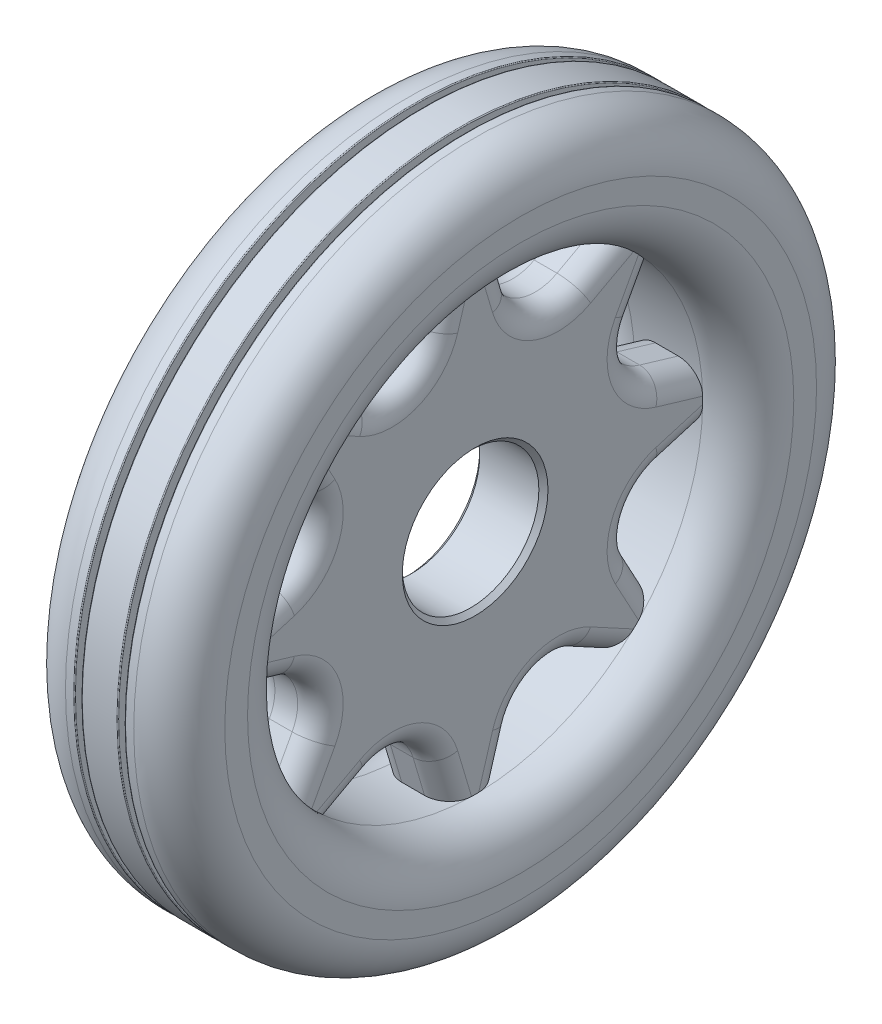
SolidWorks part; units mm, degrees
ref_plane "Front Plane" through (0, 0, 0) normal (0, 0, 1) x (1, 0, 0)
ref_plane "Top Plane" through (0, 0, 0) normal (0, 1, 0) x (1, 0, 0)
ref_plane "Right Plane" through (0, 0, 0) normal (1, 0, 0) x (0, 0, -1)
sketch "Sketch2" plane through (0, 0, 0) normal (0, 0, 1) x (1, 0, 0)
  line L0 (-23.7871, 0) -> (24.6428, 0) construction
  line L1 (24.6428, 0) -> (22.5464, 2.0963) construction
  line L2 (0, 0) -> (0, 50) construction
  line L3 (-7.5, 50) -> (7.5, 50)
  line L4 (17.5, 60) -> (17.5, 65)
  line L5 (7.5, 75) -> (-7.5, 75)
  line L6 (-17.5, 60) -> (-17.5, 65)
  arc A0 (17.5, 65) -> (7.5, 75) centre (7.5, 65) ccw
  arc A1 (7.5, 50) -> (17.5, 60) centre (7.5, 60) ccw
  arc A2 (-17.5, 65) -> (-7.5, 75) centre (-7.5, 65) cw
  arc A3 (-7.5, 50) -> (-17.5, 60) centre (-7.5, 60) cw
  point P11 (17.5, 75)
  point P14 (17.5, 50)
  point P16 (0, 75)
  dimension "D3" = 10
  dimension "D1" = 150
  dimension "D2" = 25
  dimension "D4" = 35
revolve "Revolve1" add sketch "Sketch2" angle 360 about L0
sketch "Sketch3" plane through (0, 0, 0) normal (1, 0, 0) x (0, 0, -1)
  line L0 (6, 50) -> (-6, 50)
  line L1 (-6, 50) -> (-12.1468, 29.3249)
  line L2 (0, 0) -> (0, 23.674) construction
  line L3 (6, 50) -> (12.1468, 29.3249)
  line L4 (31.1127, 39.598) -> (12.1468, 29.3249)
  line L5 (39.598, 31.1127) -> (29.3249, 12.1468)
  line L6 (39.598, 31.1127) -> (31.1127, 39.598)
  line L7 (50, 6) -> (29.3249, 12.1468)
  line L8 (50, -6) -> (29.3249, -12.1468)
  line L9 (50, -6) -> (50, 6)
  line L10 (39.598, -31.1127) -> (29.3249, -12.1468)
  line L11 (31.1127, -39.598) -> (12.1468, -29.3249)
  line L12 (31.1127, -39.598) -> (39.598, -31.1127)
  line L13 (6, -50) -> (12.1468, -29.3249)
  line L14 (-6, -50) -> (-12.1468, -29.3249)
  line L15 (-6, -50) -> (6, -50)
  line L16 (-31.1127, -39.598) -> (-12.1468, -29.3249)
  line L17 (-39.598, -31.1127) -> (-29.3249, -12.1468)
  line L18 (-39.598, -31.1127) -> (-31.1127, -39.598)
  line L19 (-50, -6) -> (-29.3249, -12.1468)
  line L20 (-50, 6) -> (-29.3249, 12.1468)
  line L21 (-50, 6) -> (-50, -6)
  line L22 (-39.598, 31.1127) -> (-29.3249, 12.1468)
  line L23 (-31.1127, 39.598) -> (-12.1468, 29.3249)
  line L24 (-31.1127, 39.598) -> (-39.598, 31.1127)
  line L25 (0, 22.7455) -> (9.5256, 17.5859)
  line L26 (-16.0835, 16.0835) -> (-19.1707, 5.6995)
  line L27 (-16.0835, 16.0835) -> (-5.6995, 19.1707)
  line L28 (-22.7455, 0) -> (-17.5859, -9.5256)
  line L29 (-22.7455, 0) -> (-17.5859, 9.5256)
  line L30 (-16.0835, -16.0835) -> (-5.6995, -19.1707)
  line L31 (-16.0835, -16.0835) -> (-19.1707, -5.6995)
  line L32 (0, -22.7455) -> (9.5256, -17.5859)
  line L33 (0, -22.7455) -> (-9.5256, -17.5859)
  line L34 (16.0835, -16.0835) -> (19.1707, -5.6995)
  line L35 (16.0835, -16.0835) -> (5.6995, -19.1707)
  line L36 (22.7455, 0) -> (17.5859, 9.5256)
  line L37 (22.7455, 0) -> (17.5859, -9.5256)
  line L38 (16.0835, 16.0835) -> (5.6995, 19.1707)
  line L39 (16.0835, 16.0835) -> (19.1707, 5.6995)
  line L40 (0, 22.7455) -> (-9.5256, 17.5859)
  circle A0 centre (0, 0) radius 50 construction
  circle A1 centre (0, 0) radius 20
  point P10 (0, 50)
  point P41 (0, 0)
  dimension "D2" = 40
  dimension "D1" = 6
  dimension "D3" = 8
extrude "Boss-Extrude1" add sketch "Sketch3" along normal blind 7.5 and the other way blind 7.5 contours L3 L4 L6 L5 L7 L9 L8 L10 L12 L11 L13 L15 L14 L16 L18 L17 L19 L21 L20 L22 L24 L23 L1 L0
fillet "Fillet1" radius 10 8 edges at (0, 29.3249, 12.1468) (0, 12.1468, 29.3249) (0, -12.1468, 29.3249) (0, -29.3249, 12.1468) (0, -29.3249, -12.1468) (0, -12.1468, -29.3249) (0, 12.1468, -29.3249) (0, 29.3249, -12.1468)
sketch "Sketch4" plane through (7.5, 0, 0) normal (1, 0, 0) x (0, 0, -1)
  circle A0 centre (0, 0) radius 15
  dimension "D1" = 30
extrude "Cut-Extrude1" cut sketch "Sketch4" against normal blind 20 and the other way blind 7.5
chamfer "Chamfer1" distance 1 angle 45 2 edges at (-7.5, 0, -15) (7.5, 0, -15)
fillet "Fillet2" radius 5 48 edges at (7.5, -37.3031, 26.8759) (7.5, -45.3814, 7.3731) (7.5, 7.3731, -45.3814) (7.5, 26.8759, -37.3031) (7.5, -26.8759, -37.3031) (7.5, -7.3731, -45.3814) (7.5, -45.3814, -7.3731) (7.5, -37.3031, -26.8759) (7.5, -7.3731, 45.3814) (7.5, -26.8759, 37.3031) (7.5, 26.8759, 37.3031) (7.5, 7.3731, 45.3814) (7.5, 45.3814, 7.3731) (7.5, 37.3031, 26.8759) (-7.5, 37.3031, 26.8759) (-7.5, 45.3814, 7.3731) (-7.5, 7.3731, 45.3814) (-7.5, 26.8759, 37.3031) (-7.5, -26.8759, 37.3031) (-7.5, -7.3731, 45.3814) (-7.5, -45.3814, 7.3731) (-7.5, -37.3031, 26.8759) (-7.5, -37.3031, -26.8759) (-7.5, -45.3814, -7.3731) (-7.5, -7.3731, -45.3814) (-7.5, -26.8759, -37.3031) (-7.5, 26.8759, -37.3031) (-7.5, 7.3731, -45.3814) (-7.5, 45.3814, -7.3731) (-7.5, 37.3031, -26.8759) (7.5, 37.3031, -26.8759) (7.5, 45.3814, -7.3731) (7.5, -34.7486, 14.3933) (7.5, 14.3933, -34.7486) (7.5, -14.3933, -34.7486) (7.5, -34.7486, -14.3933) (7.5, -14.3933, 34.7486) (7.5, 14.3933, 34.7486) (7.5, 34.7486, 14.3933) (-7.5, 34.7486, 14.3933) (-7.5, 14.3933, 34.7486) (-7.5, -14.3933, 34.7486) (-7.5, -34.7486, 14.3933) (-7.5, -34.7486, -14.3933) (-7.5, -14.3933, -34.7486) (-7.5, 14.3933, -34.7486) (-7.5, 34.7486, -14.3933) (7.5, 34.7486, -14.3933)
sketch "Sketch6" plane through (0, 0, 0) normal (0, 0, 1) x (1, 0, 0)
  line L0 (7.5, 75) -> (-7.5, 75) construction
  line L1 (-5.5, 75) -> (-4, 75)
  line L2 (-5.5, 75) -> (-5.5, 72)
  line L3 (-5.5, 72) -> (-4, 72)
  line L4 (-4, 75) -> (-4, 72)
  line L5 (-7.5, 75) -> (-7.5, -75) construction
  line L6 (4, 75) -> (5.5, 75)
  line L7 (4, 75) -> (4, 72)
  line L8 (4, 72) -> (5.5, 72)
  line L9 (5.5, 75) -> (5.5, 72)
  line L11 (0, 0) -> (26.622, 0) construction
  dimension "D1" = 8
  dimension "D2" = 1.5
  dimension "D3" = 1.5
  dimension "D4" = 3
  dimension "D5" = 3
  dimension "D6" = 3.5
revolve "Cut-Revolve1" cut sketch "Sketch6" angle 360 about L11
fillet "Fillet3" radius 0.2 8 edges at (4, 0, 75) (4, 0, 72) (5.5, 0, 75) (5.5, 0, 72) (-4, 0, 75) (-4, 0, 72) (-5.5, 0, 75) (-5.5, 0, 72)
scale "Scale1" scale about centroid uniform scaling yes scale factor 0.35
